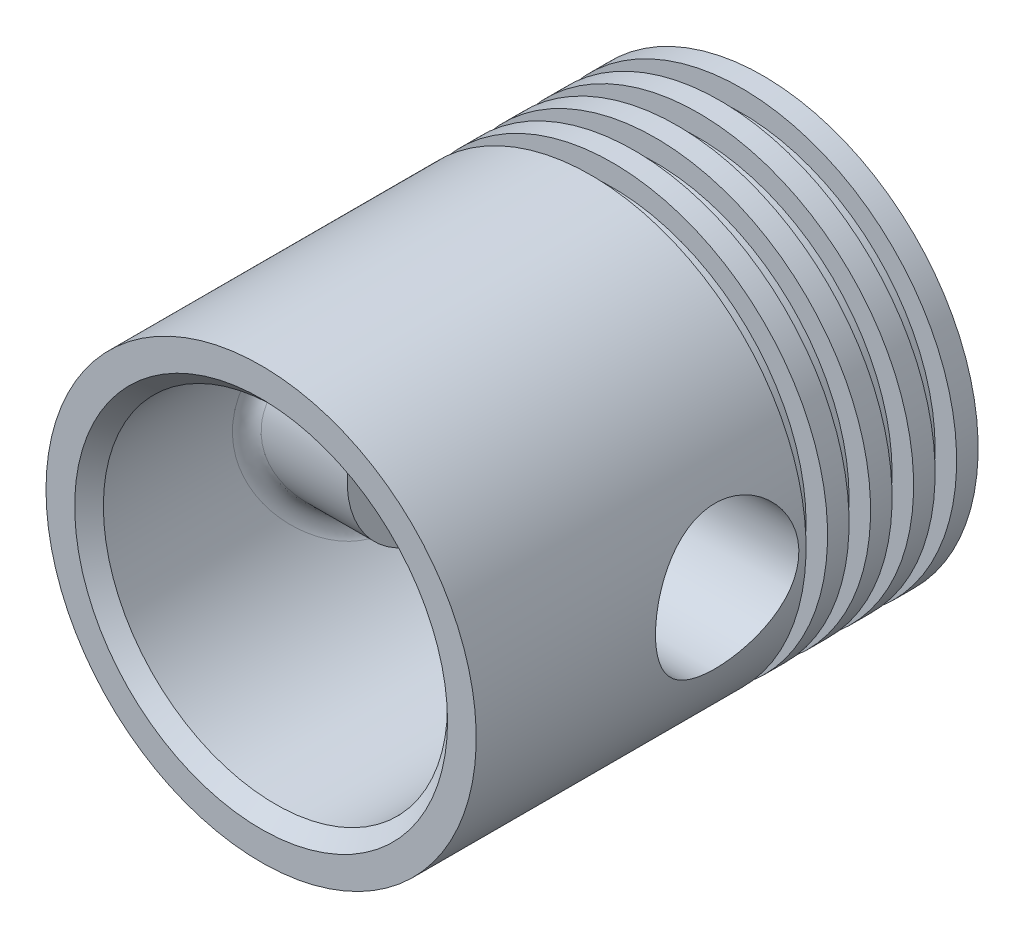
SolidWorks part; units mm, degrees
ref_plane "Front Plane" through (0, 0, 0) normal (0, 0, 1) x (1, 0, 0)
ref_plane "Top Plane" through (0, 0, 0) normal (0, 1, 0) x (1, 0, 0)
ref_plane "Right Plane" through (0, 0, 0) normal (1, 0, 0) x (0, 0, -1)
sketch "Sketch2" plane through (0, 0, 0) normal (0, 1, 0) x (1, 0, 0)
  line L0 (0, 0) -> (0, 46)
  line L1 (0, 46) -> (3, 46)
  line L2 (3, 46) -> (3, 49)
  line L3 (3, 49) -> (0, 49)
  line L4 (0, 49) -> (0, 52)
  line L5 (0, 52) -> (3, 52)
  line L6 (3, 52) -> (3, 55)
  line L7 (3, 55) -> (0, 55)
  line L8 (0, 55) -> (0, 58)
  line L9 (0, 58) -> (3, 58)
  line L10 (3, 58) -> (3, 61)
  line L11 (3, 61) -> (0, 61)
  line L12 (0, 61) -> (0, 64)
  line L13 (0, 64) -> (3, 64)
  line L14 (3, 64) -> (3, 67)
  line L15 (3, 67) -> (0, 67)
  line L16 (0, 67) -> (0, 70)
  line L17 (0, 70) -> (30, 70)
  line L20 (6, 58) -> (6, 0)
  line L21 (6, 0) -> (0, 0)
  line L22 (6, 58) -> (30, 58)
  line L24 (30, 70) -> (30, 58)
  line L25 (30, 70) -> (30, -18.745) construction
  line L26 (0, -33) -> (0, 33) construction
  point P15 (0, 35)
  point P21 (1.5, 49)
  point P24 (6, 35)
  dimension "D1" = 3
  dimension "D2" = 3
  dimension "D3" = 6
  dimension "D4" = 3
  dimension "D5" = 3
  dimension "D6" = 3
  dimension "D7" = 3
  dimension "D8" = 3
  dimension "D9" = 3
  dimension "D10" = 3
  dimension "D11" = 3
  dimension "D12" = 3
  dimension "D13" = 3
  dimension "D14" = 46
  dimension "D15" = 12
  dimension "D16" = 30
  dimension "D17" = 35
revolve "Revolve2" add sketch "Sketch2" angle 360 about L25
sketch "Sketch4" plane through (0, 0, 0) normal (1, 0, 0) x (0, 0, -1)
  circle A0 centre (35, 0) radius 10
extrude "Cut-Extrude1" cut sketch "Sketch4" along normal through all
sketch "Sketch6" plane through (0, 0, 0) normal (0, 1, 0) x (1, 0, 0)
ref_plane "Plane1" through (5, 0, 0) normal (1, 0, 0) x (0, 0, -1)
sketch "Sketch9" plane through (5, 0, 0) normal (1, 0, 0) x (0, 0, -1)
  circle A0 centre (35, 0) radius 13
extrude "Boss-Extrude2" add sketch "Sketch9" along normal blind 50
sketch "Sketch10" plane through (0, 0, 0) normal (1, 0, 0) x (0, 0, -1)
  circle A0 centre (35, 0) radius 10
extrude "Cut-Extrude2" cut sketch "Sketch10" along normal through all
sketch "Sketch11" plane through (0, 0, 0) normal (0, 0, 1) x (1, 0, 0)
  line L0 (-60, 0) -> (60, 0)
  line L2 (20, -17.6427) -> (40, -17.6427)
  line L3 (20, -17.6427) -> (20, 17.6427)
  line L4 (20, 17.6427) -> (40, 17.6427)
  line L5 (40, -17.6427) -> (40, 17.6427)
  line L6 (20, -17.6427) -> (40, 17.6427) construction
  line L7 (20, 17.6427) -> (40, -17.6427) construction
  circle A0 centre (30, 0) radius 30 construction
  point P0 (30, 0)
  point P7 (0, 0)
  point P9 (30, 0)
  dimension "D1" = 30
  dimension "D2" = 20
extrude "Cut-Extrude3" cut sketch "Sketch11" against normal blind 50 contours L2 L5 L0 L3 | L0 L5 L4 L3
fillet "Fillet1" radius 2 1 edges at (6, 0, -58)
fillet "Fillet2" radius 2 1 edges at (53.9772, 1.0448, -47.958)
fillet "Fillet3" radius 2 1 edges at (6.0228, -1.0448, -47.958)
chamfer "Chamfer1" distance 2 angle 45 1 edges at (6, 0, 0)
